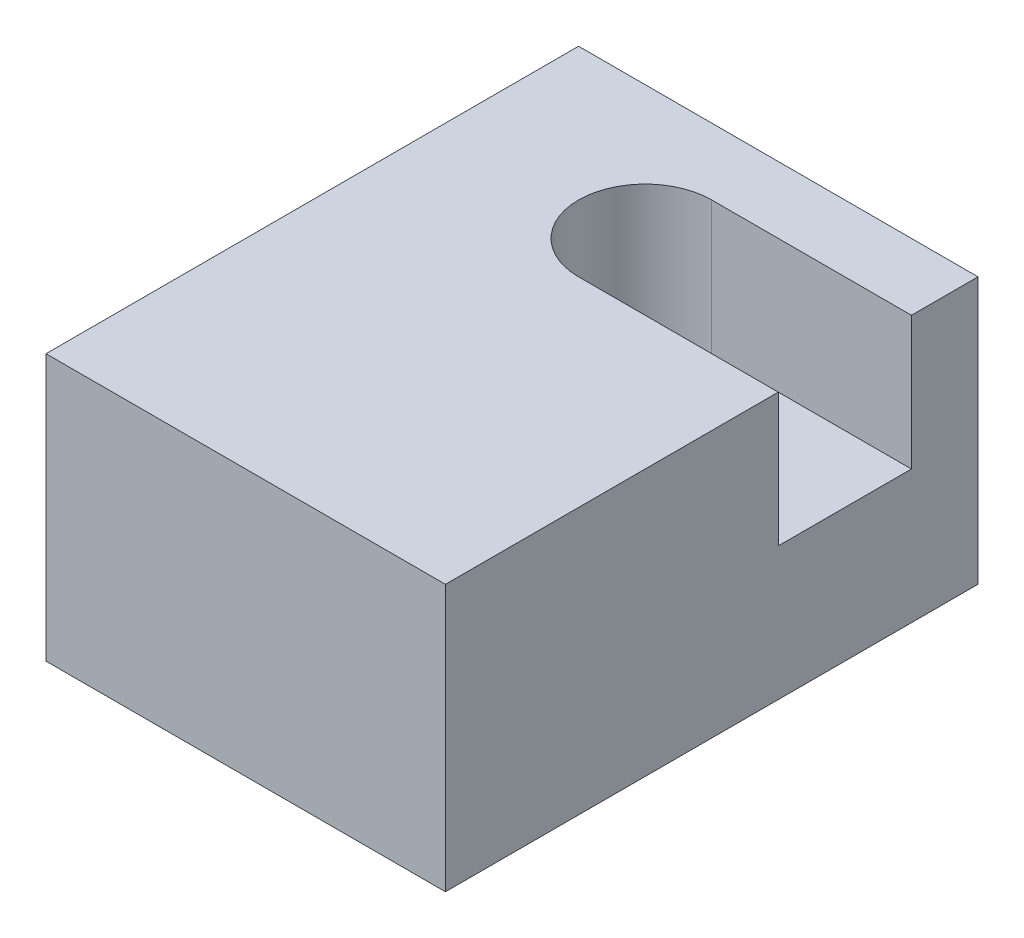
SolidWorks part; units mm, degrees
material "6061 Alloy"
ref_plane "Front Plane" through (0, 0, 0) normal (0, 0, 1) x (1, 0, 0)
ref_plane "Top Plane" through (0, 0, 0) normal (0, 1, 0) x (1, 0, 0)
ref_plane "Right Plane" through (0, 0, 0) normal (1, 0, 0) x (0, 0, -1)
sketch "Sketch1" plane through (0, 0, 0) normal (0, 0, 1) x (1, 0, 0)
  line L1 (-19.05, 12.7) -> (19.05, 12.7)
  line L2 (-19.05, 12.7) -> (-19.05, -12.7)
  line L3 (-19.05, -12.7) -> (19.05, -12.7)
  line L4 (19.05, 12.7) -> (19.05, -12.7)
  line L5 (-19.05, 12.7) -> (19.05, -12.7) construction
  line L6 (-19.05, -12.7) -> (19.05, 12.7) construction
  point P0 (0, 0)
  dimension "D1" = 38.1
  dimension "D2" = 25.4
extrude "Boss-Extrude1" add sketch "Sketch1" along normal blind 50.8
sketch "Sketch2" plane through (0, 12.7, 0) normal (0, 1, 0) x (1, 0, 0)
  line L0 (19.05, -6.35) -> (0, -6.35)
  line L1 (19.05, -50.8) -> (19.05, 0) construction
  line L2 (0, -19.05) -> (19.05, -19.05)
  line L3 (19.05, -19.05) -> (19.05, -6.35)
  line L4 (19.05, 0) -> (-19.05, 0) construction
  arc A0 (0, -6.35) -> (0, -19.05) centre (0, -12.7) ccw
  dimension "D1" = 6.35
  dimension "D2" = 19.05
  dimension "D3" = 12.7
extrude "Cut-Extrude1" cut sketch "Sketch2" against normal blind 12.7
